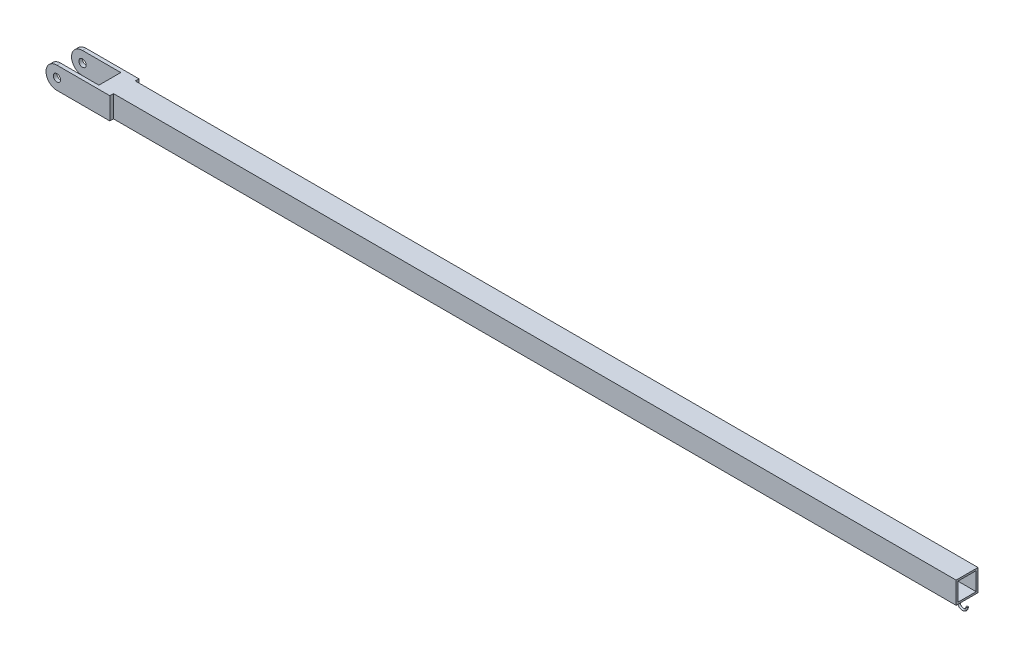
SolidWorks part; units mm, degrees
material "3003-O"
ref_plane "Front Plane" through (0, 0, 0) normal (0, 0, 1) x (1, 0, 0)
ref_plane "Top Plane" through (0, 0, 0) normal (0, 1, 0) x (1, 0, 0)
ref_plane "Right Plane" through (0, 0, 0) normal (1, 0, 0) x (0, 0, -1)
sketch "Sketch2" plane through (0, 0, 0) normal (1, 0, 0) x (0, 0, -1)
  line L1 (19.05, -19.05) -> (-19.05, -19.05)
  line L2 (19.05, -19.05) -> (19.05, 19.05)
  line L3 (19.05, 19.05) -> (-19.05, 19.05)
  line L4 (-19.05, -19.05) -> (-19.05, 19.05)
  line L5 (19.05, -19.05) -> (-19.05, 19.05) construction
  line L6 (19.05, 19.05) -> (-19.05, -19.05) construction
  point P0 (0, 0)
  dimension "D1" = 38.1
extrude "Boss-Extrude1" add sketch "Sketch2" against normal blind 1492.25
shell "Shell1" thickness 3.175 removed face at (0, 0, 0) removed face at (-1492.25, 0, 0)
sketch "Sketch3" plane through (0, 0, 19.05) normal (0, 0, 1) x (1, 0, 0)
  line L0 (0, 0) -> (-1558.925, 0) construction
  line L1 (0, 19.05) -> (0, -19.05) construction
  line L2 (-1492.25, 19.05) -> (-1466.85, 19.05)
  line L3 (-1492.25, 19.05) -> (0, 19.05) construction
  line L4 (-1466.85, 19.05) -> (-1466.85, -19.05)
  line L5 (-1492.25, -19.05) -> (0, -19.05) construction
  line L6 (-1466.85, -19.05) -> (-1492.25, -19.05)
  line L7 (-1492.25, -19.05) -> (-1558.925, -19.05)
  line L8 (-1558.925, 19.05) -> (-1492.25, 19.05)
  arc A0 (-1558.925, -19.05) -> (-1558.925, 19.05) centre (-1558.925, 0) cw
  dimension "D1" = 1558.925
  dimension "D2" = 25.4
extrude "Boss-Extrude2" add sketch "Sketch3" along normal blind 6.35
mirror "Mirror1" about plane through (0, 0, 0) normal (0, 0, 1) of "Boss-Extrude2"
sketch "Sketch4" plane through (0, 0, 25.4) normal (0, 0, 1) x (1, 0, 0)
  circle A0 centre (-1558.925, 0) radius 6.35
  dimension "D1" = 12.7
extrude "Cut-Extrude1" cut sketch "Sketch4" against normal through all
sketch "Sketch5" plane through (0, 0, 0) normal (0, 0, 1) x (1, 0, 0)
  line L0 (0, -19.05) -> (-14.2875, -19.05) construction
  line L1 (-1466.85, -19.05) -> (0, -19.05) construction
  line L2 (-14.2875, -19.05) -> (-14.2875, -38.1) construction
  line L3 (0, 19.05) -> (0, -19.05) construction
  line L4 (-14.2875, -38.1) -> (3.2196, -38.1) construction
  line L5 (-14.2875, -30.9563) -> (-14.2875, -19.05)
  arc A0 (-14.2875, -30.9563) -> (0, -30.9563) centre (-7.1437, -30.9563) ccw
  dimension "D1" = 14.2875
  dimension "D2" = 19.05
sketch "Sketch7" plane through (0, -19.05, 0) normal (0, -1, 0) x (1, 0, 0)
  circle A0 centre (-14.2875, 0) radius 1.5875
  dimension "D1" = 3.175
sweep "Sweep1" add profiles "Sketch7" path "Sketch5"
ref_axis "Axis1" through (-1558.925, 0, -23.7132) along (0, 0, 1)
ref_plane "Plane1" through (-343.5926, 646.2037, 0) normal (-0.4695, 0.8829, 0) x (0, 0, 1)
ref_plane "Plane2" through (0, 0, 0) normal (0, 1, 0) x (1, 0, 0)
